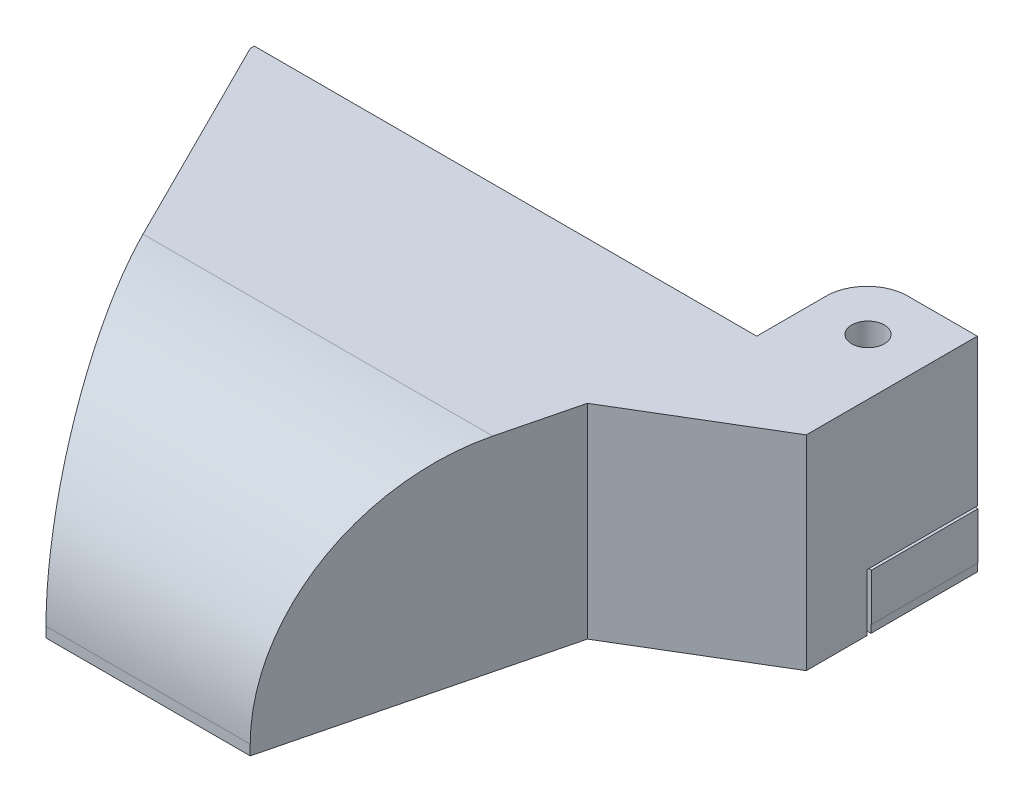
SolidWorks part; units mm, degrees
ref_plane "前视基准面" through (0, 0, 0) normal (0, 0, 1) x (1, 0, 0)
ref_plane "上视基准面" through (0, 0, 0) normal (0, 1, 0) x (1, 0, 0)
ref_plane "右视基准面" through (0, 0, 0) normal (1, 0, 0) x (0, 0, -1)
other "Configuration Table"
sketch "草图1" plane through (0, 0, 0) normal (0, 1, 0) x (1, 0, 0)
  line L1 (0, 0) -> (30, 0)
  line L2 (0, 0) -> (0, -6)
  line L3 (0, -6) -> (30, -6)
  line L4 (30, 0) -> (30, -6)
  dimension "D1" = 30
  dimension "D2" = 6
extrude "凸台-拉伸1" add sketch "草图1" along normal blind 2
sketch "草图2" plane through (0, 2, 0) normal (0, 1, 0) x (1, 0, 0)
  line L0 (30, -6) -> (30, 0) construction
  line L1 (30, 0) -> (0, 0) construction
  circle A0 centre (27.25, -3) radius 0.8
  dimension "D2" = 1.6
  dimension "D3" = 3
  dimension "D1" = 2.75
extrude "切除-拉伸1" cut sketch "草图2" against normal blind 2
sketch "草图3" plane through (0, 2, 0) normal (0, 1, 0) x (1, 0, 0)
  line L0 (0, 0) -> (0, -6) construction
  line L1 (0, -5.8) -> (1.6, -5.8)
  line L2 (0, -5.8) -> (0, -6)
  line L3 (0, -6) -> (1.6, -6)
  line L4 (1.6, -5.8) -> (1.6, -6)
  line L5 (0, -6) -> (30, -6) construction
  line L6 (30, 0) -> (0, 0) construction
  line L7 (30, -6) -> (30, 0) construction
  line L8 (23.4, -6) -> (25, -6)
  line L9 (23.4, -6) -> (23.4, -5.8)
  line L10 (23.4, -5.8) -> (25, -5.8)
  line L11 (25, -6) -> (25, -5.8)
  dimension "D1" = 1.6
  dimension "D2" = 5.8
  dimension "D3" = 5.8
  dimension "D4" = 1.6
  dimension "D5" = 5
extrude "凸台-拉伸2" add sketch "草图3" along normal blind 10
sketch "草图4" plane through (0, 12, 0) normal (0, 1, 0) x (1, 0, 0)
  line L1 (1.6, -5.8) -> (23.4, -5.8)
  line L2 (1.6, -5.8) -> (1.6, -6)
  line L3 (1.6, -6) -> (23.4, -6)
  line L4 (23.4, -5.8) -> (23.4, -6)
extrude "凸台-拉伸3" add sketch "草图4" against normal blind 1.6
sketch "草图5" plane through (0, 2, 0) normal (0, 1, 0) x (1, 0, 0)
  line L1 (25, -5.8) -> (30, -5.8)
  line L2 (25, -5.8) -> (25, -6)
  line L3 (25, -6) -> (30, -6)
  line L4 (30, -5.8) -> (30, -6)
extrude "凸台-拉伸4" add sketch "草图5" along normal blind 10
sketch "草图6" plane through (0, 0, 5.8) normal (0, 0, -1) x (-1, 0, 0)
  line L1 (-30, 12) -> (-24.6, 12)
  line L2 (-30, 12) -> (-30, 4.8)
  line L3 (-30, 4.8) -> (-24.6, 4.8)
  line L4 (-24.6, 12) -> (-24.6, 4.8)
  dimension "D1" = 5.4
  dimension "D2" = 7.2
extrude "凸台-拉伸5" add sketch "草图6" along normal blind 5.4
fillet "圆角1" radius 2 1 edges at (24.6, 8.4, 0.4)
sketch "草图7" plane through (0, 4.8, 0) normal (0, -1, 0) x (-1, 0, 0)
  circle A0 centre (-27.25, -3) radius 0.8
extrude "切除-拉伸2" cut sketch "草图7" against normal through all
sketch "草图8" plane through (0, 0, 0) normal (-1, 0, 0) x (0, 0, 1)
  line L1 (0, 2) -> (6, 2)
  line L2 (0, 2) -> (0, 0)
  line L3 (0, 0) -> (6, 0)
  line L4 (6, 2) -> (6, 0)
extrude "切除-拉伸3" cut sketch "草图8" against normal through all
sketch "草图9" plane through (0, 0, 6) normal (0, 0, 1) x (1, 0, 0)
  line L0 (23.4, 10.4) -> (23.4, 2) construction
  line L1 (1.6, 2) -> (23.4, 2)
  line L2 (1.6, 2) -> (1.6, 3.6)
  line L3 (1.6, 3.6) -> (23.4, 3.6)
  line L4 (23.4, 2) -> (23.4, 3.6)
  dimension "D1" = 1.6
extrude "凸台-拉伸7" add sketch "草图9" against normal up to surface (0.2 mm away) up to face at (15.92, 6.24, 5.8)
ref_plane "分割" through (0, 0, 6) normal (0, 0, 1) x (1, 0, 0)
sketch "草图11" plane through (0, 2, 0) normal (0, -1, 0) x (-1, 0, 0)
  line L0 (0, -6) -> (-10, -26)
  line L1 (-10, -26) -> (-20, -26)
  line L2 (-20, -26) -> (-25, -6)
  line L3 (0, -6) -> (-30, -6) construction
  line L4 (-25, -6) -> (0, -6)
  point P7 (-15, -26)
  dimension "D3" = 20
  dimension "D1" = 1.6
  dimension "D4" = 10
  dimension "D2" = 15
extrude "凸台-拉伸9" add sketch "草图11" against normal blind 1.6
sketch "草图12" plane through (0, 3.6, 0) normal (0, 1, 0) x (1, 0, 0)
  line L11 (2.5889, -7.6) -> (10.9889, -24.4)
  line L12 (10.9889, -24.4) -> (18.7508, -24.4)
  line L13 (18.7508, -24.4) -> (22.9508, -7.6)
  line L16 (23.4, -5.8) -> (1.6, -5.8)
  line L17 (1.6, -5.8) -> (1.6, -6)
  line L18 (1.6, -6) -> (0, -6)
  line L19 (0, -6) -> (10, -26)
  line L20 (10, -26) -> (20, -26)
  line L21 (20, -26) -> (25, -6)
  line L22 (25, -6) -> (23.4, -6)
  line L23 (23.4, -6) -> (23.4, -5.8)
  line L26 (1.6, -6) -> (0, -6)
  line L27 (0, -6) -> (10, -26)
  line L28 (10, -26) -> (20, -26)
  line L29 (20, -26) -> (25, -6)
  line L30 (25, -6) -> (23.4, -6)
  line L32 (2.5889, -7.6) -> (1.6, -6)
  line L33 (22.9508, -7.6) -> (23.4, -6)
  line L35 (21.8, -7.4) -> (3.2, -7.4) construction
  line L36 (21.8, -7.6) -> (21.8, -7.4) construction
  line L37 (22.9508, -7.6) -> (21.8, -7.6) construction
  line L38 (23.4, -5.8) -> (1.6, -5.8) construction
  line L39 (23.4, -6) -> (23.4, -5.8) construction
  line L40 (3.2, -7.6) -> (2.5889, -7.6) construction
  line L41 (3.2, -7.4) -> (3.2, -7.6) construction
  line L42 (1.6, -5.8) -> (1.6, -6) construction
  dimension "D1" = 0
  dimension "D2" = 1.6
extrude "凸台-拉伸10" add sketch "草图12" along normal up to surface (8.4 mm away) up to face at (27.25, 12, 2.2)
sketch "草图13" plane through (0, 12, 0) normal (0, 1, 0) x (1, 0, 0)
  line L16 (1.6, -5.8) -> (1.6, -6)
  line L17 (1.6, -6) -> (2.5889, -7.6)
  line L18 (2.5889, -7.6) -> (10.9889, -24.4)
  line L19 (10.9889, -24.4) -> (18.7508, -24.4)
  line L20 (18.7508, -24.4) -> (22.9508, -7.6)
  line L21 (22.9508, -7.6) -> (23.4, -6)
  line L22 (23.4, -6) -> (23.4, -5.8)
  line L23 (23.4, -5.8) -> (1.6, -5.8)
  line L24 (1.6, -5.8) -> (1.6, -6)
  line L25 (1.6, -6) -> (2.5889, -7.6)
  line L26 (2.5889, -7.6) -> (10.9889, -24.4)
  line L27 (10.9889, -24.4) -> (18.7508, -24.4)
  line L28 (18.7508, -24.4) -> (22.9508, -7.6)
  line L29 (22.9508, -7.6) -> (23.4, -6)
  line L30 (23.4, -6) -> (23.4, -5.8)
  line L31 (23.4, -5.8) -> (1.6, -5.8)
  dimension "D1" = 0
extrude "凸台-拉伸11" add sketch "草图13" against normal blind 1.6
sketch "草图15" plane through (0, 2, 0) normal (0, -1, 0) x (1, 0, 0)
  line L0 (10.9889, 24.4) -> (18.7508, 24.4)
  line L1 (18.7508, 24.4) -> (19.7508, 20.4)
  line L2 (19.7508, 20.4) -> (8.9889, 20.4)
  line L3 (8.9889, 20.4) -> (10.9889, 24.4)
  line L4 (20, 26) -> (10, 26) construction
  line L5 (10, 26) -> (0, 6) construction
  line L6 (25, 6) -> (20, 26) construction
  dimension "D1" = 1.6
  dimension "D2" = 180
  dimension "D3" = 180
  dimension "D4" = 1.6
  dimension "D5" = 1.6
  dimension "D6" = 4
extrude "切除-拉伸4" cut sketch "草图15" against normal blind 1.6
fillet "圆角2" radius 9 1 edges at (14.8698, 10.4, 24.4)
fillet "圆角3" radius 9.5 1 edges at (15, 12, 26)
fillet "圆角4" radius 1 1 edges at (14.3698, 3.6, 20.4)
chamfer "倒角1" distance 7 angle 45 1 edges at (25, 7, 6) first distance on face at (22.3766, 6.4935, 16.4935)
sketch "草图16" plane through (0, 2, 0) normal (0, -1, 0) x (-1, 0, 0)
  line L1 (-24.7346, -5.6086) -> (-30, -5.6086)
  line L2 (-24.7346, -5.6086) -> (-24.7346, -0.4)
  line L3 (-24.7346, -0.4) -> (-30, -0.4)
  line L4 (-30, -5.6086) -> (-30, -0.4)
extrude "凸台-拉伸12" add sketch "草图16" against normal blind 0.4 separate body
sketch "草图17" plane through (0, 2.4, 0) normal (0, 1, 0) x (1, 0, 0)
  line L0 (30, -5.6086) -> (24.7346, -5.6086) construction
  line L1 (24.7346, -0.4) -> (25.5346, -0.4)
  line L2 (24.7346, -0.4) -> (24.7346, -5.6086)
  line L3 (24.7346, -5.6086) -> (25.5346, -5.6086)
  line L4 (25.5346, -0.4) -> (25.5346, -5.6086)
  line L5 (26.2346, -0.4) -> (26.2346, -5.6086)
  line L6 (26.2346, -0.4) -> (27.0346, -0.4)
  line L7 (27.0346, -0.4) -> (27.0346, -5.6086)
  line L8 (26.2346, -5.6086) -> (27.0346, -5.6086)
  line L9 (27.7346, -0.4) -> (27.7346, -5.6086)
  line L10 (27.7346, -0.4) -> (28.5346, -0.4)
  line L11 (28.5346, -0.4) -> (28.5346, -5.6086)
  line L12 (27.7346, -5.6086) -> (28.5346, -5.6086)
  line L13 (29.2346, -0.4) -> (29.2346, -5.6086)
  line L14 (29.2346, -0.4) -> (30.0346, -0.4)
  line L15 (30.0346, -0.4) -> (30.0346, -5.6086)
  line L16 (29.2346, -5.6086) -> (30.0346, -5.6086)
  dimension "D1" = 0.8
  dimension "D2" = 4
extrude "凸台-拉伸13" add sketch "草图17" along normal blind 2.3
equation "\"D2@草图11\"=\"D1@草图1\"/2"
